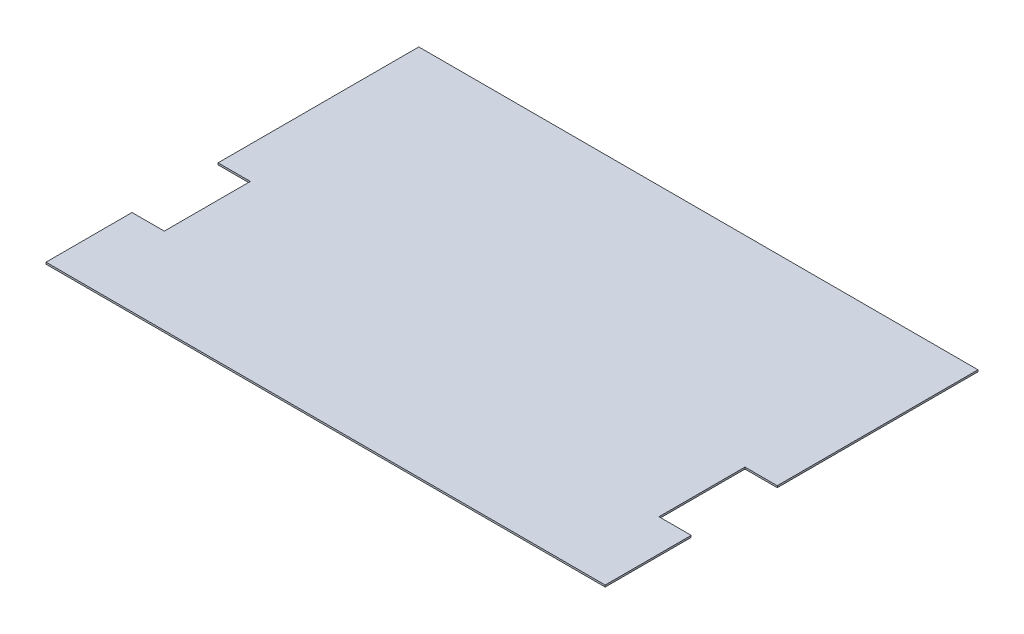
SolidWorks part; units mm, degrees
ref_plane "Front Plane" through (0, 0, 0) normal (0, 0, 1) x (1, 0, 0)
ref_plane "Top Plane" through (0, 0, 0) normal (0, 1, 0) x (1, 0, 0)
ref_plane "Right Plane" through (0, 0, 0) normal (1, 0, 0) x (0, 0, -1)
sketch "Sketch1" plane through (0, 0, 0) normal (0, 1, 0) x (1, 0, 0)
  line L0 (219.075, -88.9) -> (247.65, -88.9)
  line L1 (-247.65, 88.9) -> (247.65, 88.9)
  line L2 (-247.65, 88.9) -> (-247.65, -88.9)
  line L3 (-247.65, -88.9) -> (-219.075, -88.9)
  line L4 (247.65, 88.9) -> (247.65, -88.9)
  line L5 (-247.65, 88.9) -> (247.65, -88.9) construction
  line L6 (-247.65, -88.9) -> (247.65, 88.9) construction
  line L7 (219.075, -165.1) -> (247.65, -165.1)
  line L8 (-219.075, -88.9) -> (-219.075, -165.1)
  line L10 (219.075, -88.9) -> (219.075, -165.1)
  line L11 (-247.65, -165.1) -> (-219.075, -165.1)
  line L12 (-247.65, -165.1) -> (-247.65, -241.3)
  line L13 (-247.65, -241.3) -> (247.65, -241.3)
  line L14 (247.65, -165.1) -> (247.65, -241.3)
  point P0 (0, 0)
  dimension "D1" = 177.8
  dimension "D2" = 495.3
  dimension "D3" = 28.575
  dimension "D4" = 28.575
base flange "Base-Flange1" sketch "Sketch1" thickness 1.5875 reverse thickness direction no parameters "D1"=254
sketch "Bend-Lines1" [suppressed] plane through (0, 0, 0) normal (0, 1, 0) x (1, 0, 0)
sketch "Bounding-Box1" [suppressed] plane through (0, 0, 0) normal (0, 1, 0) x (1, 0, 0)
sheet metal parameters "Sheet-Metal1" thickness 1.5875 parameters "D1"=254
flat pattern "Flat-Pattern1" [suppressed]
sketch "Bend-Lines2" plane through (0, 0, 0) normal (0, 1, 0) x (1, 0, 0)
sketch3d "Bounding-Box2" [suppressed]
  line L0 (247.65, -241.3, 0) -> (-247.65, -241.3, 0) construction
  line L1 (247.65, 88.9, 0) -> (-247.65, 88.9, 0) construction
  line L2 (247.65, -241.3, 0) -> (247.65, 88.9, 0) construction
  line L3 (-247.65, -241.3, 0) -> (-247.65, 88.9, 0) construction
